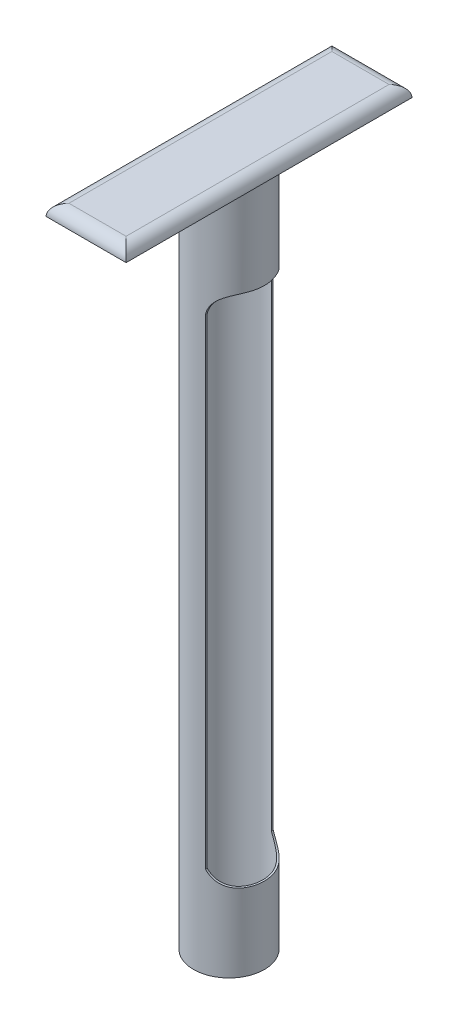
SolidWorks part; units mm, degrees
ref_plane "Front Plane" through (0, 0, 0) normal (0, 0, 1) x (1, 0, 0)
ref_plane "Top Plane" through (0, 0, 0) normal (0, 1, 0) x (1, 0, 0)
ref_plane "Right Plane" through (0, 0, 0) normal (1, 0, 0) x (0, 0, -1)
sketch "Sketch1" plane through (0, 0, 0) normal (0, 1, 0) x (1, 0, 0)
  circle A0 centre (0, 0) radius 15.5
  circle A1 centre (0, 0) radius 14.75
extrude "Boss-Extrude1" add sketch "Sketch1" along normal blind 300
sketch "Sketch2" plane through (0, 0, 0) normal (0, 0, 1) x (1, 0, 0)
  line L0 (-15.5, 0) -> (4.5, 0) construction
  line L1 (4.5, 0) -> (4.5, 393.6565) construction
  line L2 (-15.5, 300) -> (-15.5, 250) construction
  line L3 (-15.5, 300) -> (-15.5, 0) construction
  line L4 (-15.5, 250) -> (15.5, 250) construction
  line L5 (15.5, 0) -> (15.5, 300) construction
  line L6 (-15.5, 0) -> (-15.5, 40) construction
  line L7 (-15.5, 40) -> (15.5, 40) construction
  line L9 (15.5, 33.5597) -> (15.5, 259.0863)
  line L10 (4.5, 40) -> (4.5, 250)
  line L13 (-15.5, 0) -> (-15.5, 33.5597) construction
  line L14 (-15.5, 33.5597) -> (15.5, 33.5597) construction
  line L16 (-11, 259.0863) -> (15.5, 259.0863) construction
  arc A2 (15.5, 259.0863) -> (4.5, 250) centre (15.5, 247.8848) ccw
  arc A3 (15.5, 33.5597) -> (4.5, 40) centre (15.5, 46.1739) cw
sketch "Sketch4" plane through (0, 300, 0) normal (0, 1, 0) x (1, 0, 0)
  line L1 (-17.5, -62.5) -> (17.5, -62.5)
  line L2 (-17.5, -62.5) -> (-17.5, 62.5)
  line L3 (-17.5, 62.5) -> (17.5, 62.5)
  line L4 (17.5, -62.5) -> (17.5, 62.5)
  line L5 (-17.5, -62.5) -> (17.5, 62.5) construction
  line L6 (-17.5, 62.5) -> (17.5, -62.5) construction
  point P0 (0, 0)
extrude "Boss-Extrude2" add sketch "Sketch4" along normal blind 5
extrude "Cut-Extrude2" cut sketch "Sketch2" against normal blind 40 and the other way blind 50
fillet "Fillet2" radius 5 4 edges at (0, 305, -62.5) (0, 305, 62.5) (-17.5, 305, 0) (17.5, 305, 0)
